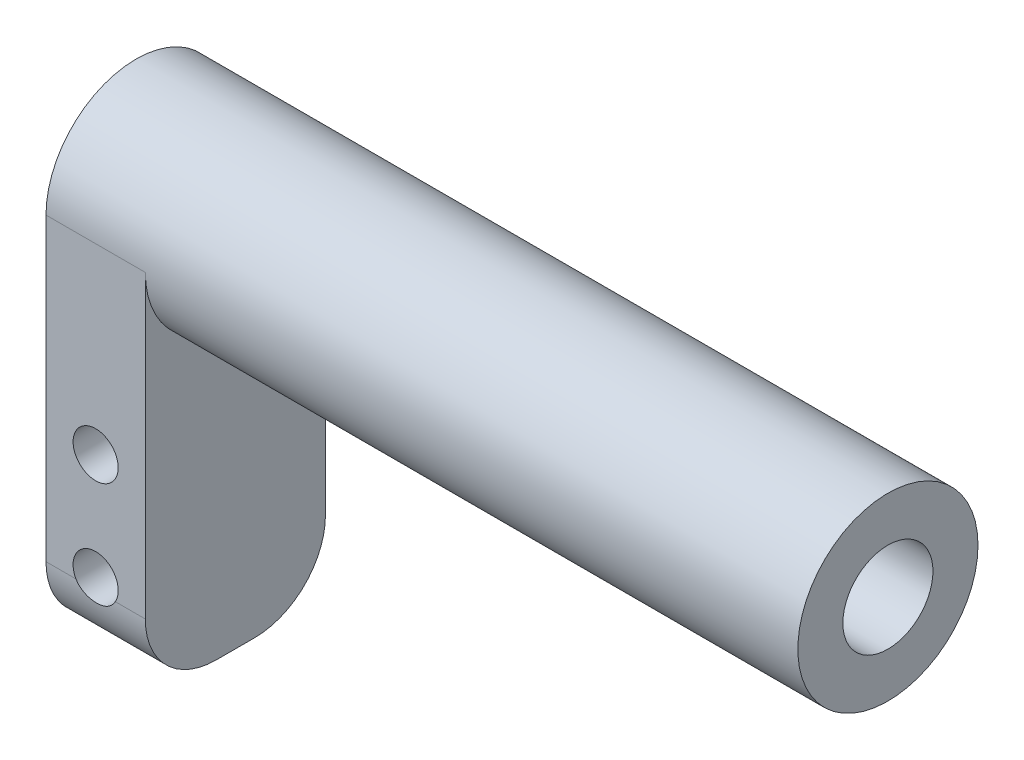
SolidWorks part; units mm, degrees
material "ABS"
ref_plane "Front Plane" through (0, 0, 0) normal (1, 0, 0) x (0, 1, 0)
ref_plane "Top Plane" through (0, 0, 0) normal (0, 0, 1) x (0, 1, 0)
ref_plane "Right Plane" through (0, 0, 0) normal (0, 1, 0) x (-1, 0, 0)
sketch "Sketch1" plane through (0, 0, 0) normal (1, 0, 0) x (0, 1, 0)
  circle A0 centre (0, 0) radius 3.175
  circle A1 centre (0, 0) radius 3
  circle A2 centre (0, 0) radius 6.35
  dimension "D1" = 6
  dimension "D2" = 6.35
  dimension "D3" = 12.7
extrude "Boss-Extrude1" add sketch "Sketch1" along normal blind 53 contours A2 A0 region at (0, -6.1704, 0)
extrude "Boss-Extrude2" add sketch "Sketch1<3>" along normal blind 7 contours A0 A1 region at (0, -3.0852, 0)
sketch "Sketch1<3>" plane through (0, 0, 0) normal (1, 0, 0) x (0, 1, 0) same geometry as "Sketch1"
sketch "Sketch10" plane through (0, 0, 0) normal (-1, 0, 0) x (0, -1, 0)
  line L0 (0, 6.35) -> (26.16, 6.35)
  line L2 (26.16, 6.35) -> (26.16, -6.35)
  line L3 (26.16, -6.35) -> (0, -6.35)
  circle A0 centre (0, 0) radius 6.35 construction
  arc A2 (0, 6.35) -> (0, -6.35) centre (0, 0) cw
  point P2 (26.1518, 6.1542)
  point P3 (0, 0)
  point P8 (0, 0)
  point P9 (0, 0)
  dimension "D1" = 26.16
extrude "Boss-Extrude3" add sketch "Sketch10" against normal blind 7 contours L0 A2 L3 L2 region at (0, -15.5262, 0)
fillet "Fillet2" radius 5 2 edges at (3.5, -26.16, 6.35) (3.5, -26.16, -6.35)
sketch "Sketch11" plane through (0, 0, -6.35) normal (0, 0, -1) x (1, 0, 0)
  line L0 (0, 0) -> (53, 0) construction
  line L1 (53, -6.35) -> (53, 6.35) construction
  line L2 (3.5, 21.16) -> (3.5, 0) construction
  line L3 (7, 21.16) -> (0, 21.16) construction
  circle A0 centre (3.5, 20.38) radius 1.59
  circle A1 centre (3.5, 12.88) radius 1.59
  dimension "D3" = 3.18
  dimension "D4" = 3.18
  dimension "D1" = 12.88
  dimension "D2" = 7.5
extrude "Cut-Extrude5" cut sketch "Sketch11" against normal through all
sketch "Sketch14" plane through (0, 0, 0) normal (-1, 0, 0) x (0, 0, 1)
  line L0 (0.5112, -3.2591) -> (0.3942, -3.8443)
  line L1 (0, 0) -> (0, -3.9) construction
  line L2 (0, 0) -> (0.5602, -3.2689) construction
  line L3 (0.6032, -3.2433) -> (0.9083, -3.7562)
  line L4 (-0.6343, -3.2373) -> (-0.9444, -3.7473)
  line L5 (-0.5425, -3.254) -> (-0.4312, -3.8403)
  line L6 (-1.7033, -2.8251) -> (-2.1691, -3.1983)
  line L7 (-1.6227, -2.8722) -> (-1.7186, -3.4613)
  line L8 (-2.5669, -2.0722) -> (-3.1322, -2.2635)
  line L9 (-2.5072, -2.144) -> (-2.7988, -2.6647)
  line L10 (-3.1208, -1.0693) -> (-3.7174, -1.0558)
  line L11 (-3.0893, -1.1572) -> (-3.5414, -1.5468)
  line L12 (-3.2983, 0.0625) -> (-3.8543, 0.2793)
  line L13 (-3.2988, -0.0308) -> (-3.8569, -0.2422)
  line L14 (-3.078, 1.1869) -> (-3.5264, 1.5808)
  line L15 (-3.1104, 1.0993) -> (-3.7071, 1.0915)
  line L16 (-2.4865, 2.168) -> (-2.773, 2.6915)
  line L17 (-2.5468, 2.0968) -> (-3.1102, 2.2936)
  line L18 (-1.595, 2.8877) -> (-1.6852, 3.4776)
  line L19 (-1.6761, 2.8414) -> (-2.1382, 3.219)
  line L20 (-0.5112, 3.2591) -> (-0.3942, 3.8443)
  line L21 (-0.6032, 3.2433) -> (-0.9083, 3.7562)
  line L22 (0.6343, 3.2373) -> (0.9444, 3.7473)
  line L23 (0.5425, 3.254) -> (0.4312, 3.8403)
  line L24 (1.7033, 2.8251) -> (2.1691, 3.1983)
  line L25 (1.6227, 2.8722) -> (1.7186, 3.4613)
  line L26 (2.5669, 2.0722) -> (3.1322, 2.2635)
  line L27 (2.5072, 2.144) -> (2.7988, 2.6647)
  line L28 (3.1208, 1.0693) -> (3.7174, 1.0558)
  line L29 (3.0893, 1.1572) -> (3.5414, 1.5468)
  line L30 (3.2983, -0.0625) -> (3.8543, -0.2793)
  line L31 (3.2988, 0.0308) -> (3.8569, 0.2422)
  line L32 (3.078, -1.1869) -> (3.5264, -1.5808)
  line L33 (3.1104, -1.0993) -> (3.7071, -1.0915)
  line L34 (2.4865, -2.168) -> (2.773, -2.6915)
  line L35 (2.5468, -2.0968) -> (3.1102, -2.2936)
  line L36 (1.595, -2.8877) -> (1.6852, -3.4776)
  line L37 (1.6761, -2.8414) -> (2.1382, -3.219)
  line L38 (-0.0375, -3.8998) -> (0, -3.9)
  line L39 (-1.3691, -3.6518) -> (-1.3339, -3.6648)
  line L40 (-2.5355, -2.9633) -> (-2.5069, -2.9876)
  line L41 (-3.3775, -1.95) -> (-3.3961, -1.9174)
  line L42 (-3.8408, -0.6772) -> (-3.8471, -0.6402)
  line L43 (-3.8408, 0.6772) -> (-3.8341, 0.7142)
  line L44 (-3.3775, 1.95) -> (-3.3586, 1.9824)
  line L45 (-2.5069, 2.9876) -> (-2.478, 3.0116)
  line L46 (-1.3339, 3.6648) -> (-1.2985, 3.6775)
  line L47 (0, 3.9) -> (0.0375, 3.8998)
  line L48 (1.3339, 3.6648) -> (1.3691, 3.6518)
  line L49 (2.5069, 2.9876) -> (2.5355, 2.9633)
  line L50 (3.3775, 1.95) -> (3.3961, 1.9174)
  line L51 (3.8408, 0.6772) -> (3.8471, 0.6402)
  line L52 (3.8408, -0.6772) -> (3.8341, -0.7142)
  line L53 (3.3775, -1.95) -> (3.3586, -1.9824)
  line L54 (2.5069, -2.9876) -> (2.478, -3.0116)
  line L55 (1.3339, -3.6648) -> (1.2985, -3.6775)
  arc A0 (0.3496, -3.8843) -> (0, -3.9) centre (0, 0) cw
  arc A1 (0.3496, -3.8843) -> (0.3942, -3.8443) centre (0.3452, -3.8345) ccw
  arc A2 (0.5112, -3.2591) -> (0.6032, -3.2433) centre (0.5602, -3.2689) cw
  arc A3 (0.4199, -3.8983) -> (0.3942, -3.8443) centre (0.4432, -3.8541) cw
  arc A4 (0.4199, -3.8983) -> (0.7367, -4.0472) centre (2.2357, -0.4468) ccw
  arc A6 (0.9636, -3.7791) -> (0.9083, -3.7562) centre (0.9513, -3.7306) cw
  arc A7 (0.9636, -3.7791) -> (1.2985, -3.6775) centre (0, 0) ccw
  arc A8 (-0.9999, -3.7696) -> (-1.3339, -3.6648) centre (0, 0) cw
  arc A9 (-0.9999, -3.7696) -> (-0.9444, -3.7473) centre (-0.9871, -3.7213) ccw
  arc A10 (-0.6343, -3.2373) -> (-0.5425, -3.254) centre (-0.5916, -3.2633) cw
  arc A11 (-0.387, -3.8808) -> (-0.4312, -3.8403) centre (-0.3821, -3.831) cw
  arc A12 (-0.387, -3.8808) -> (-0.0375, -3.8998) centre (0, 0) ccw
  arc A13 (-2.2289, -3.2003) -> (-2.5069, -2.9876) centre (0, 0) cw
  arc A14 (-2.2289, -3.2003) -> (-2.1691, -3.1983) centre (-2.2004, -3.1593) ccw
  arc A15 (-1.7033, -2.8251) -> (-1.6227, -2.8722) centre (-1.6721, -2.8642) cw
  arc A16 (-1.691, -3.5143) -> (-1.7186, -3.4613) centre (-1.6693, -3.4693) cw
  arc A17 (-1.691, -3.5143) -> (-1.3691, -3.6518) centre (0, 0) ccw
  arc A18 (-3.1891, -2.245) -> (-3.3775, -1.95) centre (0, 0) cw
  arc A19 (-3.1891, -2.245) -> (-3.1322, -2.2635) centre (-3.1482, -2.2162) ccw
  arc A20 (-2.5669, -2.0722) -> (-2.5072, -2.144) centre (-2.5508, -2.1196) cw
  arc A21 (-2.791, -2.7241) -> (-2.7988, -2.6647) centre (-2.7552, -2.6891) cw
  arc A22 (-2.791, -2.7241) -> (-2.5355, -2.9633) centre (0, 0) ccw
  arc A23 (-3.7646, -1.0188) -> (-3.8408, -0.6772) centre (0, 0) cw
  arc A24 (-3.7646, -1.0188) -> (-3.7174, -1.0558) centre (-3.7163, -1.0058) ccw
  arc A25 (-3.1208, -1.0693) -> (-3.0893, -1.1572) centre (-3.1219, -1.1193) cw
  arc A26 (-3.5543, -1.6052) -> (-3.5414, -1.5468) centre (-3.5088, -1.5846) cw
  arc A27 (-3.5543, -1.6052) -> (-3.3961, -1.9174) centre (0, 0) ccw
  arc A28 (-3.886, 0.3302) -> (-3.8408, 0.6772) centre (0, 0) cw
  arc A29 (-3.886, 0.3302) -> (-3.8543, 0.2793) centre (-3.8362, 0.3259) ccw
  arc A30 (-3.2983, 0.0625) -> (-3.2988, -0.0308) centre (-3.3165, 0.016) cw
  arc A31 (-3.889, -0.2928) -> (-3.8569, -0.2422) centre (-3.8391, -0.289) cw
  arc A32 (-3.889, -0.2928) -> (-3.8471, -0.6402) centre (0, 0) ccw
  arc A33 (-3.5387, 1.6393) -> (-3.3775, 1.95) centre (0, 0) cw
  arc A34 (-3.5387, 1.6393) -> (-3.5264, 1.5808) centre (-3.4934, 1.6183) ccw
  arc A35 (-3.078, 1.1869) -> (-3.1104, 1.0993) centre (-3.111, 1.1493) cw
  arc A36 (-3.7546, 1.055) -> (-3.7071, 1.0915) centre (-3.7065, 1.0415) cw
  arc A37 (-3.7546, 1.055) -> (-3.8341, 0.7142) centre (0, 0) ccw
  arc A38 (-2.7646, 2.7508) -> (-2.5069, 2.9876) centre (0, 0) cw
  arc A39 (-2.7646, 2.7508) -> (-2.773, 2.6915) centre (-2.7292, 2.7155) ccw
  arc A40 (-2.4865, 2.168) -> (-2.5468, 2.0968) centre (-2.5303, 2.144) cw
  arc A41 (-3.1673, 2.2755) -> (-3.1102, 2.2936) centre (-3.1267, 2.2464) cw
  arc A42 (-3.1673, 2.2755) -> (-3.3586, 1.9824) centre (0, 0) ccw
  arc A43 (-1.6571, 3.5305) -> (-1.3339, 3.6648) centre (0, 0) cw
  arc A44 (-1.6571, 3.5305) -> (-1.6852, 3.4776) centre (-1.6358, 3.4852) ccw
  arc A45 (-1.595, 2.8877) -> (-1.6761, 2.8414) centre (-1.6444, 2.8801) cw
  arc A46 (-2.198, 3.2216) -> (-2.1382, 3.219) centre (-2.1698, 3.1803) cw
  arc A47 (-2.198, 3.2216) -> (-2.478, 3.0116) centre (0, 0) ccw
  arc A48 (-0.3496, 3.8843) -> (0, 3.9) centre (0, 0) cw
  arc A49 (-0.3496, 3.8843) -> (-0.3942, 3.8443) centre (-0.3452, 3.8345) ccw
  arc A50 (-0.5112, 3.2591) -> (-0.6032, 3.2433) centre (-0.5602, 3.2689) cw
  arc A51 (-0.9636, 3.7791) -> (-0.9083, 3.7562) centre (-0.9513, 3.7306) cw
  arc A52 (-0.9636, 3.7791) -> (-1.2985, 3.6775) centre (0, 0) ccw
  arc A53 (0.9999, 3.7696) -> (1.3339, 3.6648) centre (0, 0) cw
  arc A54 (0.9999, 3.7696) -> (0.9444, 3.7473) centre (0.9871, 3.7213) ccw
  arc A55 (0.6343, 3.2373) -> (0.5425, 3.254) centre (0.5916, 3.2633) cw
  arc A56 (0.387, 3.8808) -> (0.4312, 3.8403) centre (0.3821, 3.831) cw
  arc A57 (0.387, 3.8808) -> (0.0375, 3.8998) centre (0, 0) ccw
  arc A58 (2.2289, 3.2003) -> (2.5069, 2.9876) centre (0, 0) cw
  arc A59 (2.2289, 3.2003) -> (2.1691, 3.1983) centre (2.2004, 3.1593) ccw
  arc A60 (1.7033, 2.8251) -> (1.6227, 2.8722) centre (1.6721, 2.8642) cw
  arc A61 (1.691, 3.5143) -> (1.7186, 3.4613) centre (1.6693, 3.4693) cw
  arc A62 (1.691, 3.5143) -> (1.3691, 3.6518) centre (0, 0) ccw
  arc A63 (3.1891, 2.245) -> (3.3775, 1.95) centre (0, 0) cw
  arc A64 (3.1891, 2.245) -> (3.1322, 2.2635) centre (3.1482, 2.2162) ccw
  arc A65 (2.5669, 2.0722) -> (2.5072, 2.144) centre (2.5508, 2.1196) cw
  arc A66 (2.791, 2.7241) -> (2.7988, 2.6647) centre (2.7552, 2.6891) cw
  arc A67 (2.791, 2.7241) -> (2.5355, 2.9633) centre (0, 0) ccw
  arc A68 (3.7646, 1.0188) -> (3.8408, 0.6772) centre (0, 0) cw
  arc A69 (3.7646, 1.0188) -> (3.7174, 1.0558) centre (3.7163, 1.0058) ccw
  arc A70 (3.1208, 1.0693) -> (3.0893, 1.1572) centre (3.1219, 1.1193) cw
  arc A71 (3.5543, 1.6052) -> (3.5414, 1.5468) centre (3.5088, 1.5846) cw
  arc A72 (3.5543, 1.6052) -> (3.3961, 1.9174) centre (0, 0) ccw
  arc A73 (3.886, -0.3302) -> (3.8408, -0.6772) centre (0, 0) cw
  arc A74 (3.886, -0.3302) -> (3.8543, -0.2793) centre (3.8362, -0.3259) ccw
  arc A75 (3.2983, -0.0625) -> (3.2988, 0.0308) centre (3.3165, -0.016) cw
  arc A76 (3.889, 0.2928) -> (3.8569, 0.2422) centre (3.8391, 0.289) cw
  arc A77 (3.889, 0.2928) -> (3.8471, 0.6402) centre (0, 0) ccw
  arc A78 (3.5387, -1.6393) -> (3.3775, -1.95) centre (0, 0) cw
  arc A79 (3.5387, -1.6393) -> (3.5264, -1.5808) centre (3.4934, -1.6183) ccw
  arc A80 (3.078, -1.1869) -> (3.1104, -1.0993) centre (3.111, -1.1493) cw
  arc A81 (3.7546, -1.055) -> (3.7071, -1.0915) centre (3.7065, -1.0415) cw
  arc A82 (3.7546, -1.055) -> (3.8341, -0.7142) centre (0, 0) ccw
  arc A83 (2.7646, -2.7508) -> (2.5069, -2.9876) centre (0, 0) cw
  arc A84 (2.7646, -2.7508) -> (2.773, -2.6915) centre (2.7292, -2.7155) ccw
  arc A85 (2.4865, -2.168) -> (2.5468, -2.0968) centre (2.5303, -2.144) cw
  arc A86 (3.1673, -2.2755) -> (3.1102, -2.2936) centre (3.1267, -2.2464) cw
  arc A87 (3.1673, -2.2755) -> (3.3586, -1.9824) centre (0, 0) ccw
  arc A88 (1.6571, -3.5305) -> (1.3339, -3.6648) centre (0, 0) cw
  arc A89 (1.6571, -3.5305) -> (1.6852, -3.4776) centre (1.6358, -3.4852) ccw
  arc A90 (1.595, -2.8877) -> (1.6761, -2.8414) centre (1.6444, -2.8801) cw
  arc A91 (2.198, -3.2216) -> (2.1382, -3.219) centre (2.1698, -3.1803) cw
  arc A92 (2.198, -3.2216) -> (2.478, -3.0116) centre (0, 0) ccw
  point P207 (0, 0)
  dimension "D1" = 3.9
  dimension "D2" = 0.05
  dimension "D3" = 0.05
  dimension "D4" = 0.04
  dimension "D5" = 18
  dimension "D6" = 0.5968
  dimension "D8" = 0.35
extrude "Cut-Extrude6" cut sketch "Sketch14" against normal blind 15 contours A91 A92 L54 A83 A84 L34 A85 L35 A86 A87 L53 A78 A79 L32 A80 L33 A81 A82 L52 A73 A74 L30 A75 L31 A76 A77 L51 A68 A69 L28 A70 L29 A71 A72 L50 A63 A64 L26 A65 L27 A66 A67 L49 A58 A59 L24 A60 L25 A61 A62 L48 region at (0, 0, 0)
